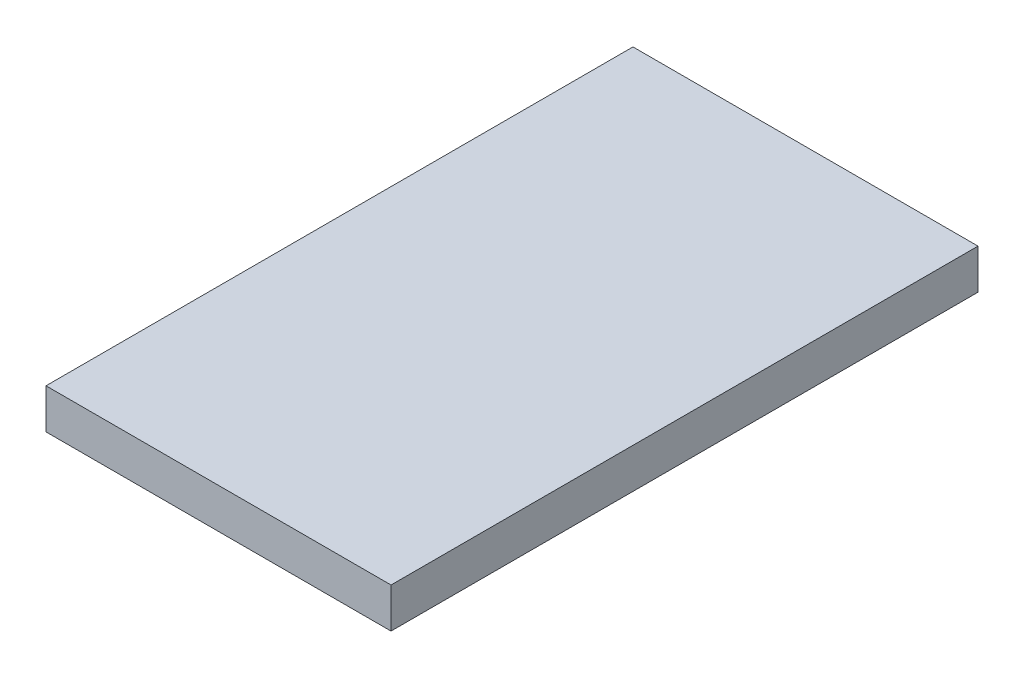
SolidWorks part; units mm, degrees
ref_plane "Front Plane" through (0, 0, 0) normal (0, 0, 1) x (1, 0, 0)
ref_plane "Top Plane" through (0, 0, 0) normal (0, 1, 0) x (1, 0, 0)
ref_plane "Right Plane" through (0, 0, 0) normal (1, 0, 0) x (0, 0, -1)
sketch "Sketch1" plane through (0, 0, 0) normal (0, 0, 1) x (1, 0, 0)
  line L7 (-30.861, -3.5719) -> (30.861, -3.5719)
  line L8 (-30.861, -3.5719) -> (-30.861, 3.5719)
  line L9 (-30.861, 3.5719) -> (30.861, 3.5719)
  line L10 (30.861, -3.5719) -> (30.861, 3.5719)
  line L11 (-30.861, -3.5719) -> (30.861, 3.5719) construction
  line L12 (-30.861, 3.5719) -> (30.861, -3.5719) construction
  point P4 (0, 0)
  point P14 (0, 0)
  dimension "Width" = 61.722
  dimension "Thickness" = 7.1437
sketch "Sketch2" plane through (0, 0, 0) normal (0, 1, 0) x (0, 0, -1)
  line L0 (52.5, 30.861) -> (-52.5, 30.861) construction
  point P0 (24.6525, 30.861)
  point P4 (0, 30.861)
  point P6 (-24.6525, 30.861)
  dimension "Length" = 105
  dimension "D1" = 77.1525
  dimension "D2" = 77.1525
sketch "Sketch3" plane through (0, 0, 0) normal (0, 0, 1) x (1, 0, 0)
  line L6 (-30.861, 3.5719) -> (30.861, 3.5719)
  line L7 (30.861, 3.5719) -> (30.861, -3.5719)
  line L8 (30.861, -3.5719) -> (-30.861, -3.5719)
  line L9 (-30.861, -3.5719) -> (-30.861, 3.5719)
extrude "Boss-Extrude1" add sketch "Sketch3" along normal mid plane 105
equation "\"D1@Boss-Extrude1\" = \"Length@Sketch2\""
equation "\"D1@Sketch2\"=\"Width@Sketch1\" * 1.25"
equation "\"D2@Sketch2\"=\"D1@Sketch2\""
